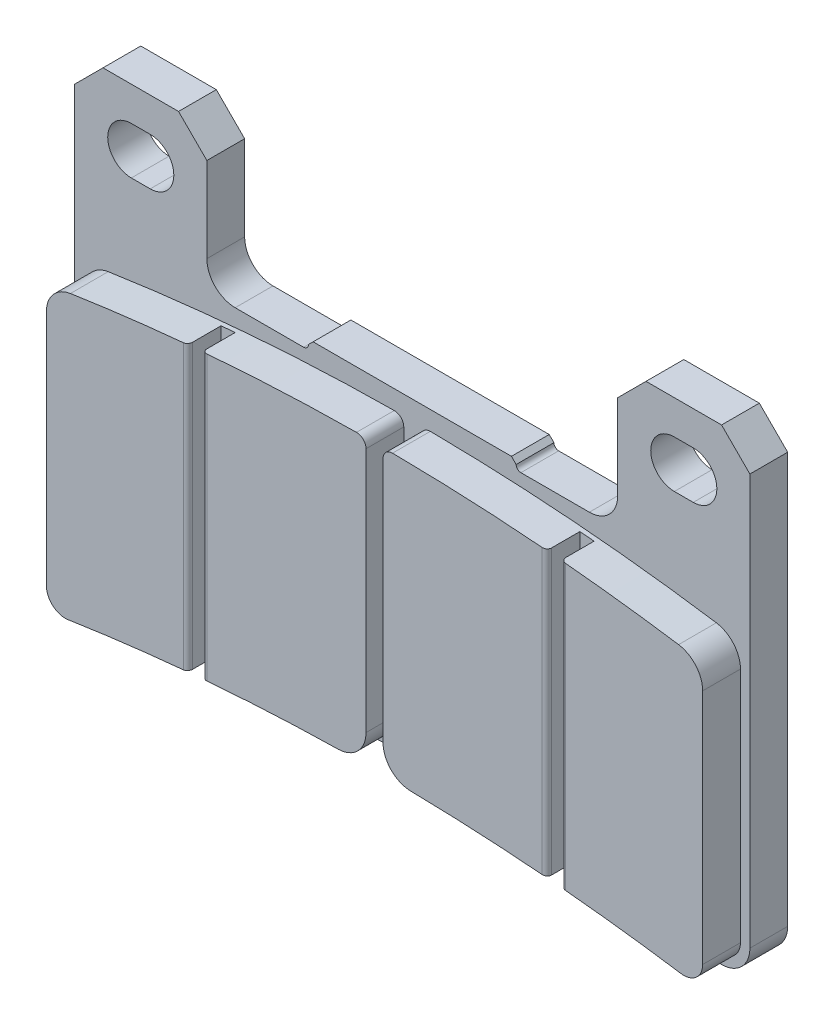
SolidWorks part; units mm, degrees
ref_plane "Front Plane" through (0, 0, 0) normal (0, 0, 1) x (1, 0, 0)
ref_plane "Top Plane" through (0, 0, 0) normal (0, 1, 0) x (1, 0, 0)
ref_plane "Right Plane" through (0, 0, 0) normal (1, 0, 0) x (0, 0, -1)
sketch "Sketch1" plane through (0, 0, 0) normal (0, 0, 1) x (1, 0, 0)
  line L0 (-11, 11) -> (-11, 10)
  line L1 (-35.75, 25) -> (35.75, 25)
  line L2 (-35.75, 25) -> (-35.75, -25)
  line L3 (-35.75, -25) -> (35.75, -25)
  line L4 (35.75, 25) -> (35.75, -25)
  line L5 (-35.75, 25) -> (35.75, -25) construction
  line L6 (-35.75, -25) -> (35.75, 25) construction
  line L7 (-21.75, 39) -> (21.75, 39)
  line L8 (-21.75, 39) -> (-21.75, 11)
  line L9 (-21.75, 11) -> (21.75, 11)
  line L10 (21.75, 39) -> (21.75, 11)
  line L11 (-21.75, 39) -> (21.75, 11) construction
  line L12 (-21.75, 11) -> (21.75, 39) construction
  line L13 (-11, 10) -> (-21.75, 10)
  line L14 (-21.75, 10) -> (-21.75, 11)
  line L15 (0, 0) -> (0, 5.0671)
  line L16 (21.75, 10) -> (21.75, 11)
  line L17 (11, 10) -> (21.75, 10)
  line L18 (11, 11) -> (11, 10)
  line L19 (-29.75, 18.9) -> (-27.75, 18.9) construction
  line L20 (-29.75, 21.4) -> (-27.75, 21.4)
  line L21 (-29.75, 16.4) -> (-27.75, 16.4)
  line L22 (29.75, 18.9) -> (27.75, 18.9) construction
  line L23 (29.75, 21.4) -> (27.75, 21.4)
  line L24 (29.75, 16.4) -> (27.75, 16.4)
  line L25 (-21.75, 25.3911) -> (-35.75, 25.3911) construction
  line L26 (-35.75, 25.3911) -> (-35.75, 25) construction
  line L27 (-28.75, 25.3911) -> (-28.75, 18.9) construction
  arc A0 (-35.75, -25) -> (35.75, -25) centre (0, -236.5104) cw
  arc A1 (-29.75, 21.4) -> (-29.75, 16.4) centre (-29.75, 18.9) ccw
  arc A2 (-27.75, 16.4) -> (-27.75, 21.4) centre (-27.75, 18.9) ccw
  arc A3 (29.75, 21.4) -> (29.75, 16.4) centre (29.75, 18.9) cw
  arc A4 (27.75, 16.4) -> (27.75, 21.4) centre (27.75, 18.9) cw
  point P0 (0, 0)
  point P5 (0, 25)
  point P22 (-28.75, 18.9)
  point P29 (28.75, 18.9)
  dimension "D7" = 33
  dimension "D8" = 2.5
  dimension "D1" = 50
  dimension "D2" = 71.5
  dimension "D3" = 14
  dimension "D4" = 14
  dimension "D5" = 1
  dimension "D6" = 22
  dimension "D9" = 2
  dimension "D10" = 3.6
extrude "Boss-Extrude1" add sketch "Sketch1" along normal blind 4 contours L2 A0 L4 L1 L10 L16 L17 L18 L9 L0 L13 L14 L8 A2 L21 A1 L20 L24 A4 L23 A3 region at (0, -3.2457, 0)
chamfer "Chamfer1" distance 3 angle 45 4 edges at (35.75, 25, 2) (21.75, 25, 2) (-35.75, 25, 2) (-21.75, 25, 2)
fillet "Fillet1" radius 3 4 edges at (-35.75, -25, 2) (35.75, -25, 2) (21.75, 10, 2) (-21.75, 10, 2)
fillet "Fillet2" radius 0.5 2 edges at (11, 10, 2) (-11, 10, 2)
chamfer "Chamfer2" distance 0.5 angle 45 2 edges at (-11, 11, 2) (11, 11, 2)
sketch "Sketch2" plane through (0, 0, 4) normal (0, 0, 1) x (1, 0, 0)
  line L0 (-50.957, 2.889) -> (50.957, 2.889) construction
  line L1 (0, 0) -> (0, 2.889) construction
  line L2 (-10.5, 11) -> (10.5, 11) construction
  line L4 (-0.9, 23.9777) -> (0.9, 23.9777)
  line L5 (-0.9, 23.9777) -> (-0.9, -23.9777)
  line L6 (-0.9, -23.9777) -> (0.9, -23.9777)
  line L7 (0.9, 23.9777) -> (0.9, -23.9777)
  line L8 (-0.9, 23.9777) -> (0.9, -23.9777) construction
  line L9 (-0.9, -23.9777) -> (0.9, 23.9777) construction
  line L30 (10.0858, 10) -> (-10.0858, 10)
  line L31 (-11.5, 9) -> (-18.75, 9)
  line L32 (-22.75, 13) -> (-22.75, 21.5858)
  line L33 (-22.75, 21.5858) -> (-25.1642, 24)
  line L34 (-25.1642, 24) -> (-32.3358, 24)
  line L35 (-32.3358, 24) -> (-34.75, 21.5858)
  line L36 (-34.75, 21.5858) -> (-34.75, -21.4797)
  line L37 (34.75, -21.4797) -> (34.75, 21.5858)
  line L38 (34.75, 21.5858) -> (32.3358, 24)
  line L39 (32.3358, 24) -> (25.1642, 24)
  line L40 (25.1642, 24) -> (22.75, 21.5858)
  line L41 (22.75, 21.5858) -> (22.75, 13)
  line L42 (18.75, 9) -> (11.5, 9)
  line L43 (10.0858, 10) -> (-10.0858, 10)
  line L44 (-11.5, 9) -> (-18.75, 9)
  line L45 (-22.75, 13) -> (-22.75, 21.5858)
  line L46 (-22.75, 21.5858) -> (-25.1642, 24)
  line L47 (-25.1642, 24) -> (-32.3358, 24)
  line L48 (-32.3358, 24) -> (-34.75, 21.5858)
  line L49 (-34.75, 21.5858) -> (-34.75, -21.4797)
  line L50 (34.75, -21.4797) -> (34.75, 21.5858)
  line L51 (34.75, 21.5858) -> (32.3358, 24)
  line L52 (32.3358, 24) -> (25.1642, 24)
  line L53 (25.1642, 24) -> (22.75, 21.5858)
  line L54 (22.75, 21.5858) -> (22.75, 13)
  line L55 (18.75, 9) -> (11.5, 9)
  arc A7 (-50.957, 2.889) -> (50.957, 2.889) centre (0, -206.5104) cw
  arc A14 (-11.5, 9) -> (-10.0858, 10) centre (-11.5, 10.5) ccw
  arc A15 (-22.75, 13) -> (-18.75, 9) centre (-18.75, 13) ccw
  arc A16 (-34.75, -21.4797) -> (-32.4489, -23.4569) centre (-32.75, -21.4797) ccw
  arc A17 (32.4489, -23.4569) -> (-32.4489, -23.4569) centre (0, -236.5104) ccw
  arc A18 (32.4489, -23.4569) -> (34.75, -21.4797) centre (32.75, -21.4797) ccw
  arc A19 (18.75, 9) -> (22.75, 13) centre (18.75, 13) ccw
  arc A20 (10.0858, 10) -> (11.5, 9) centre (11.5, 10.5) ccw
  arc A21 (-11.5, 9) -> (-10.0858, 10) centre (-11.5, 10.5) ccw
  arc A22 (-22.75, 13) -> (-18.75, 9) centre (-18.75, 13) ccw
  arc A23 (-34.75, -21.4797) -> (-32.4489, -23.4569) centre (-32.75, -21.4797) ccw
  arc A24 (32.4489, -23.4569) -> (-32.4489, -23.4569) centre (0, -236.5104) ccw
  arc A25 (32.4489, -23.4569) -> (34.75, -21.4797) centre (32.75, -21.4797) ccw
  arc A26 (18.75, 9) -> (22.75, 13) centre (18.75, 13) ccw
  arc A27 (10.0858, 10) -> (11.5, 9) centre (11.5, 10.5) ccw
  dimension "D2" = 2
  dimension "D3" = 1.8
  dimension "D1" = 1
extrude "Boss-Extrude2" add sketch "Sketch2" along normal blind 4 contours A24 L5 A7 L49 A23 | A24 A25 L50 A7 L7 region at (-17.8053, -6.9429, 4) region at (17.8053, -6.9429, 4)
fillet "Fillet3" radius 3 4 edges at (-34.75, 6.1799, 6) (-0.9, -21.0019, 6) (0.9, -21.0019, 6) (34.75, 6.1799, 6)
fillet "Fillet4" radius 1 2 edges at (-0.9, 8.9981, 6) (0.9, 8.9981, 6)
sketch "Sketch3" plane through (0, 0, 4) normal (0, 0, 1) x (1, 0, 0)
  line L0 (-19, 16.01) -> (-19, -34.9905)
  line L1 (0, 0) -> (0, 20.9622) construction
  line L2 (19, 16.01) -> (19, -34.9905)
  dimension "D1" = 38
extrude "Cut-Extrude-Thin1" cut sketch "Sketch3" along normal through all from offset 0.5 thin thin type mid plane wall 1.5
fillet "Fillet5" radius 0.5 4 edges at (19.75, -6.9069, 8) (18.25, -6.7741, 8) (-19.75, -6.9069, 8) (-18.25, -6.7741, 8)
sketch "Sketch4" plane through (0, 0, 0) normal (0, 0, -1) x (-1, 0, 0)
  line L0 (-11.5, 10) -> (-18.75, 10) construction
  line L1 (-35.75, 22) -> (-35.75, -21.4797) construction
  line L2 (35.75, 22) -> (35.75, -21.4797) construction
  circle A0 centre (-16.25, 0.5) radius 3
  circle A1 centre (24.2525, 0.5) radius 3
  circle A2 centre (15.75, -13.5) radius 3
  circle A3 centre (-25.25, -13.5) radius 3
  point P10 (-35.75, 0.2602)
  point P13 (35.75, 0.2602)
  dimension "D1" = 6
  dimension "D2" = 9.5
  dimension "D3" = 19.5
  dimension "D4" = 11.5
  dimension "D5" = 20
  dimension "D6" = 10.5
  dimension "D7" = 23.5
extrude "Cut-Extrude1" cut sketch "Sketch4" against normal blind 2.5
fillet "Fillet6" radius 0.2 4 edges at (22.25, -13.5, 0) (-18.75, -13.5, 0) (-27.2525, 0.5, 0) (13.25, 0.5, 0)
